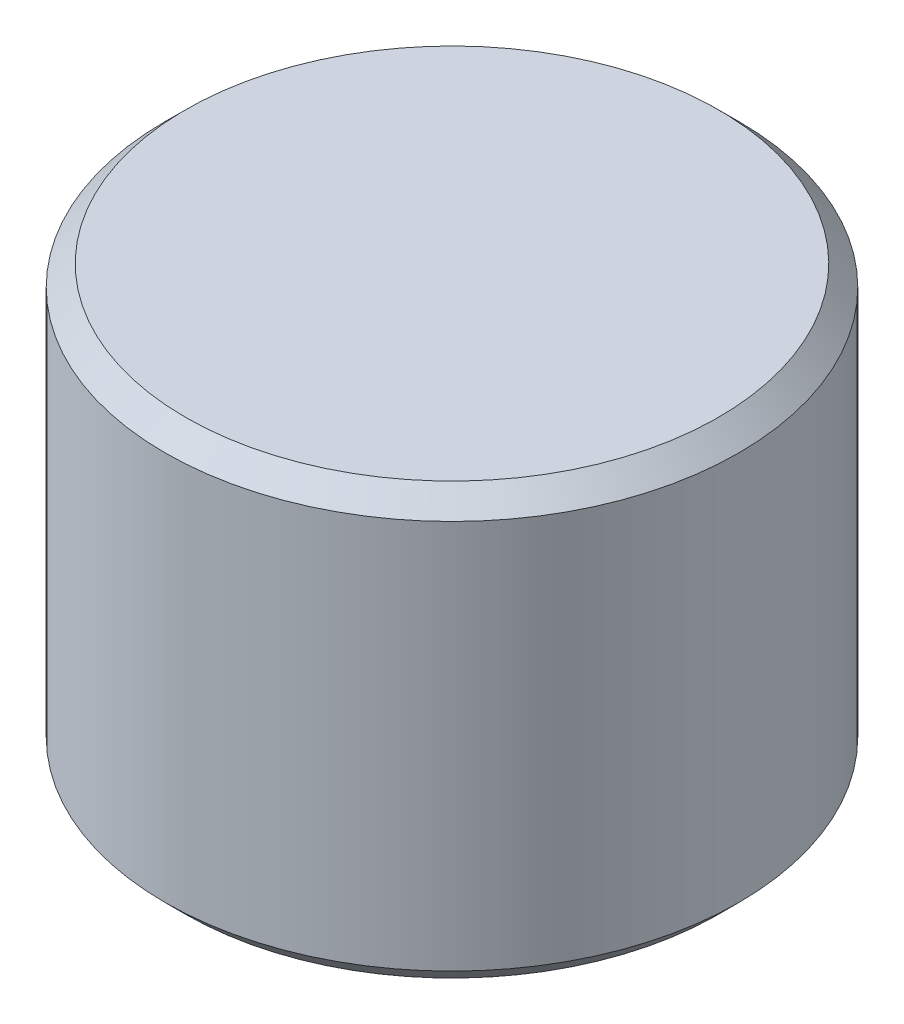
SolidWorks part; units mm, degrees
ref_plane "Front Plane" through (0, 0, 0) normal (0, 0, 1) x (1, 0, 0)
ref_plane "Top Plane" through (0, 0, 0) normal (0, 1, 0) x (1, 0, 0)
ref_plane "Right Plane" through (0, 0, 0) normal (1, 0, 0) x (0, 0, -1)
sketch "Sketch1" plane through (0, 0, 0) normal (0, 1, 0) x (1, 0, 0)
  circle A0 centre (0, 0) radius 4.2
  dimension "D1" = 8.4
extrude "Boss-Extrude1" add sketch "Sketch1" along normal blind 6.3
chamfer "Chamfer1" distance 0.3 angle 45 2 edges at (0, 0, 4.2) (0, 6.3, 4.2)
equation "\"pin_circle_R\" = 27"
equation "\"ecc\" = 1.5"
equation "\"n_pins\" = 11"
equation "\"pin_d\" = 3"
equation "\"out_pin_R\" = 18.5"
equation "\"disc_clr\" = 0.1"
equation "\"seat_6803\" = 26.1"
equation "\"disc_t\" = 5"
equation "\"out_hole_clr\" = 0.2"
equation "\"boss_17\" = 16.95"
equation "\"rotor_bolt_R\" = 10"
equation "\"m25_clr\" = 2.8"
equation "\"m25_head\" = 5"
equation "\"insert_hole\" = 4.6"
equation "\"csk\" = 0.6"
equation "\"peg_d\" = 3.0"
equation "\"plug_d\" = 8.4"
equation "\"D1@Sketch1\"=\"plug_d\""
